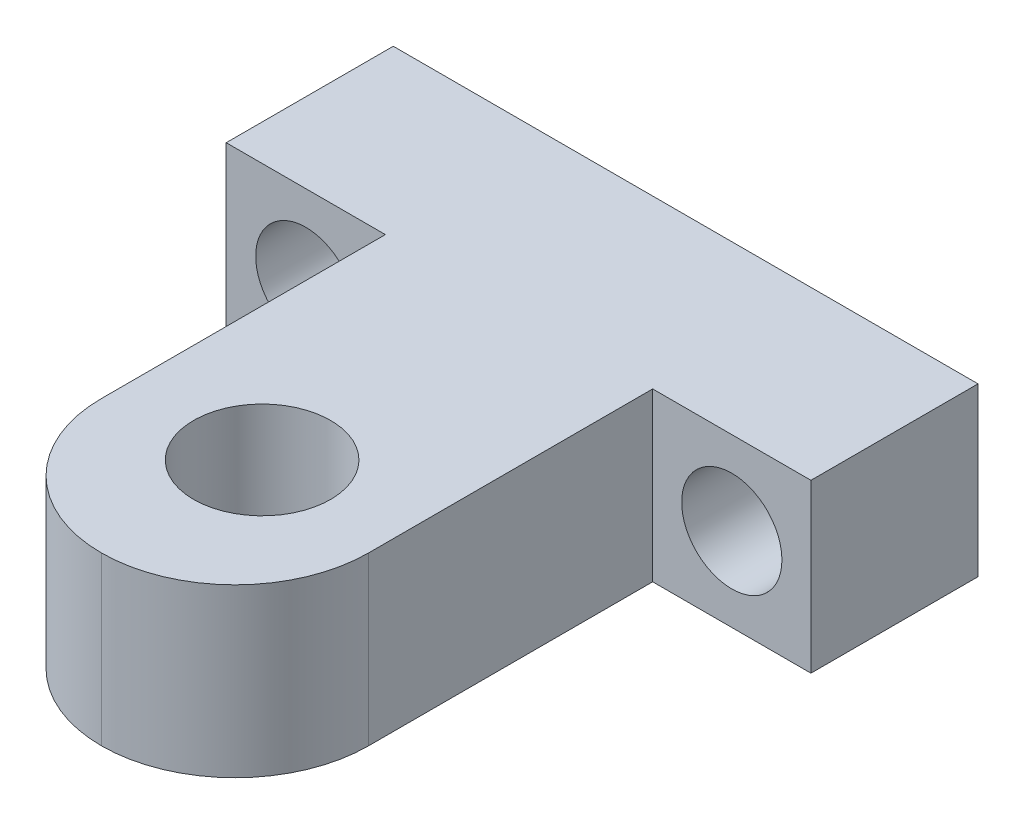
SolidWorks part; units mm, degrees
material "Custom Plastic"
ref_plane "Front Plane" through (0, 0, 0) normal (0, 0, 1) x (1, 0, 0)
ref_plane "Top Plane" through (0, 0, 0) normal (0, 1, 0) x (1, 0, 0)
ref_plane "Right Plane" through (0, 0, 0) normal (1, 0, 0) x (0, 0, -1)
sketch "Sketch1" plane through (0, 0, 315.5076) normal (0, 0, 1) x (1, 0, 0)
  line L0 (-17.5534, 0.6353) -> (-17.5534, 41.6025)
  line L4 (-42.5534, 305.4353) -> (-42.5534, 0.6353)
  line L5 (-42.5534, 0.6353) -> (262.2466, 0.6353)
  line L6 (262.2466, 0.6353) -> (262.2466, 305.4353)
  line L7 (262.2466, 305.4353) -> (-42.5534, 305.4353)
  line L8 (-42.5534, 305.4353) -> (-42.5534, 0.6353)
  line L9 (-42.5534, 0.6353) -> (262.2466, 0.6353)
  line L10 (262.2466, 0.6353) -> (262.2466, 305.4353)
  line L11 (262.2466, 305.4353) -> (-42.5534, 305.4353)
  line L13 (-17.5534, 0.6353) -> (17.4466, 0.6353) construction
  line L14 (-17.5534, 0.6353) -> (17.4466, 0.6353)
  line L15 (-17.5534, 0.6353) -> (-17.5534, 10.6353)
  line L16 (-17.5534, 10.6353) -> (17.4466, 10.6353)
  line L17 (17.4466, 0.6353) -> (17.4466, 10.6353)
  line L18 (-0.0534, 10.6353) -> (-0.0534, 0.6353) construction
  line M8 (-42.5534, 0.6353) -> (262.2466, 0.6353)
  dimension "D2" = 25
  dimension "D1" = 0
extrude "Boss-Extrude1" add sketch "Sketch1" along normal blind 10 contours L17 L16 L0 M8 region at (-0.0534, 5.6353, 315.5076)
sketch "Sketch2" plane through (0, 0, 325.5076) normal (0, 0, 1) x (1, 0, 0)
  line L0 (-0.0534, 10.6353) -> (-0.0534, 0.6353) construction
  line L1 (-17.5534, 0.6353) -> (17.4466, 0.6353) construction
  line L2 (-0.0534, 5.6353) -> (-8.0267, 5.6353)
  line L3 (-8.0267, 5.6353) -> (7.9733, 5.6353)
  line L4 (-17.5534, 10.6353) -> (17.4466, 10.6353) construction
  line L5 (7.9733, 10.6353) -> (-8.0267, 10.6353)
  line L6 (-17.5534, 0.6353) -> (17.4466, 0.6353)
  line L7 (17.4466, 0.6353) -> (17.4466, 10.6353)
  line L8 (17.4466, 10.6353) -> (-17.5534, 10.6353)
  line L9 (-17.5534, 10.6353) -> (-17.5534, 0.6353)
  line L10 (-17.5534, 0.6353) -> (17.4466, 0.6353)
  line L11 (17.4466, 0.6353) -> (17.4466, 10.6353)
  line L12 (17.4466, 10.6353) -> (-17.5534, 10.6353)
  line L13 (-17.5534, 10.6353) -> (-17.5534, 0.6353)
  line L14 (7.9733, 10.6353) -> (7.9733, 0.6353)
  line L15 (7.9733, 0.6353) -> (-8.0267, 0.6353)
  line L16 (-8.0267, 10.6353) -> (-8.0267, 0.6353)
  line M9 (17.4466, 10.6353) -> (-17.5534, 10.6353)
  dimension "D1" = 0
extrude "Boss-Extrude2" add sketch "Sketch2" along normal blind 25 contours L3 L0 L15 L14 | L16 L2 L3 L14 M9 | L14 L5 L16 L15 region at (-4.0401, 8.1353, 325.5076) region at (3.9599, 3.1353, 325.5076)
sketch "Sketch3" plane through (0, 10.6353, 0) normal (0, 1, 0) x (1, 0, 0)
  line L0 (-0.0267, -350.5076) -> (-0.0534, -315.5076) construction
  line L1 (7.9733, -325.5076) -> (7.9733, -350.5076) construction
  line L8 (17.4466, -315.5076) -> (-17.5534, -315.5076)
  line L9 (-17.5534, -315.5076) -> (-17.5534, -325.5076)
  line L10 (-17.5534, -325.5076) -> (-8.0267, -325.5076)
  line L11 (-8.0267, -325.5076) -> (-8.0267, -350.5076)
  line L12 (-8.0267, -350.5076) -> (7.9733, -350.5076)
  line L13 (7.9733, -350.5076) -> (7.9733, -325.5076)
  line L14 (7.9733, -325.5076) -> (17.4466, -325.5076)
  line L15 (17.4466, -325.5076) -> (17.4466, -315.5076)
  line L16 (17.4466, -315.5076) -> (-17.5534, -315.5076)
  line L17 (-17.5534, -315.5076) -> (-17.5534, -325.5076)
  line L18 (-17.5534, -325.5076) -> (-8.0267, -325.5076)
  line L19 (-8.0267, -325.5076) -> (-8.0267, -350.5076)
  line L20 (-8.0267, -350.5076) -> (7.9733, -350.5076)
  line L21 (7.9733, -350.5076) -> (7.9733, -325.5076)
  line L22 (7.9733, -325.5076) -> (17.4466, -325.5076)
  line L23 (17.4466, -325.5076) -> (17.4466, -315.5076)
  circle A0 centre (-0.0341, -340.8776) radius 4.1
  dimension "D2" = 25.37
  dimension "D1" = 0
extrude "Cut-Extrude3" cut sketch "Sketch3" against normal up to surface (7.9597 mm away) contours A0
sketch "Sketch4" plane through (0, 0, 325.5076) normal (0, 0, 1) x (1, 0, 0)
  line L0 (-8.0267, 10.6353) -> (-8.0267, 0.6353) construction
  line L1 (-8.0267, 0.6353) -> (-17.5534, 0.6353) construction
  line L2 (-12.7901, 0.6353) -> (-12.7901, 10.6353) construction
  line L3 (12.7099, 10.6353) -> (12.7099, 0.6353) construction
  line L4 (-8.0267, 0.6353) -> (-8.0267, 10.6353)
  line L5 (-8.0267, 10.6353) -> (-17.5534, 10.6353)
  line L6 (-17.5534, 10.6353) -> (-17.5534, 0.6353)
  line L7 (-17.5534, 0.6353) -> (-8.0267, 0.6353)
  line L8 (-8.0267, 0.6353) -> (-8.0267, 10.6353)
  line L9 (-8.0267, 10.6353) -> (-17.5534, 10.6353)
  line L10 (-17.5534, 10.6353) -> (-17.5534, 0.6353)
  line L11 (-17.5534, 0.6353) -> (-8.0267, 0.6353)
  line L12 (17.4466, 10.6353) -> (7.9733, 10.6353)
  line L13 (7.9733, 10.6353) -> (7.9733, 0.6353)
  line L14 (7.9733, 0.6353) -> (17.4466, 0.6353)
  line L15 (17.4466, 0.6353) -> (17.4466, 10.6353)
  line L16 (17.4466, 10.6353) -> (7.9733, 10.6353)
  line L17 (7.9733, 10.6353) -> (7.9733, 0.6353)
  line L18 (7.9733, 0.6353) -> (17.4466, 0.6353)
  line L19 (17.4466, 0.6353) -> (17.4466, 10.6353)
  circle A0 centre (-12.7901, 5.6353) radius 1.7
  circle A1 centre (12.7099, 5.6353) radius 1.7
  dimension "D1" = 0
  dimension "D2" = 0
extrude "Cut-Extrude4" cut sketch "Sketch4" against normal blind 13 contours A0 | A1 region at (-12.7901, 5.6353, 325.5076)
sketch "Sketch5" plane through (0, 0, 325.5076) normal (0, 0, 1) x (1, 0, 0)
  line L4 (-8.0267, 0.6353) -> (-8.0267, 10.6353)
  line L5 (-8.0267, 10.6353) -> (-17.5534, 10.6353)
  line L6 (-17.5534, 10.6353) -> (-17.5534, 0.6353)
  line L7 (-17.5534, 0.6353) -> (-8.0267, 0.6353)
  line L8 (-8.0267, 0.6353) -> (-8.0267, 10.6353)
  line L9 (-8.0267, 10.6353) -> (-17.5534, 10.6353)
  line L10 (-17.5534, 10.6353) -> (-17.5534, 0.6353)
  line L11 (-17.5534, 0.6353) -> (-8.0267, 0.6353)
  line L12 (17.4466, 10.6353) -> (7.9733, 10.6353)
  line L13 (7.9733, 10.6353) -> (7.9733, 0.6353)
  line L14 (7.9733, 0.6353) -> (17.4466, 0.6353)
  line L15 (17.4466, 0.6353) -> (17.4466, 10.6353)
  line L16 (17.4466, 10.6353) -> (7.9733, 10.6353)
  line L17 (7.9733, 10.6353) -> (7.9733, 0.6353)
  line L18 (7.9733, 0.6353) -> (17.4466, 0.6353)
  line L19 (17.4466, 0.6353) -> (17.4466, 10.6353)
  circle A0 centre (12.7099, 5.6353) radius 1.7 construction
  circle A1 centre (-12.7901, 5.6353) radius 1.7 construction
  circle A2 centre (12.7099, 5.6353) radius 1.7
  circle A3 centre (-12.7901, 5.6353) radius 1.7
  circle A4 centre (-12.7901, 5.6353) radius 3
  circle A5 centre (12.7099, 5.6353) radius 3
  circle M9 centre (-12.7901, 5.6353) radius 1.7
  dimension "D1" = 0
  dimension "D2" = 0
extrude "Cut-Extrude5" cut sketch "Sketch5" against normal blind 6 contours A4 M9 | A5 A2 region at (-15.7052, 5.6353, 325.5076) region at (9.7948, 5.6353, 325.5076)
fillet "Fillet1" radius 8 2 edges at (7.9733, 5.6353, 350.5076) (-8.0267, 5.6353, 350.5076)
